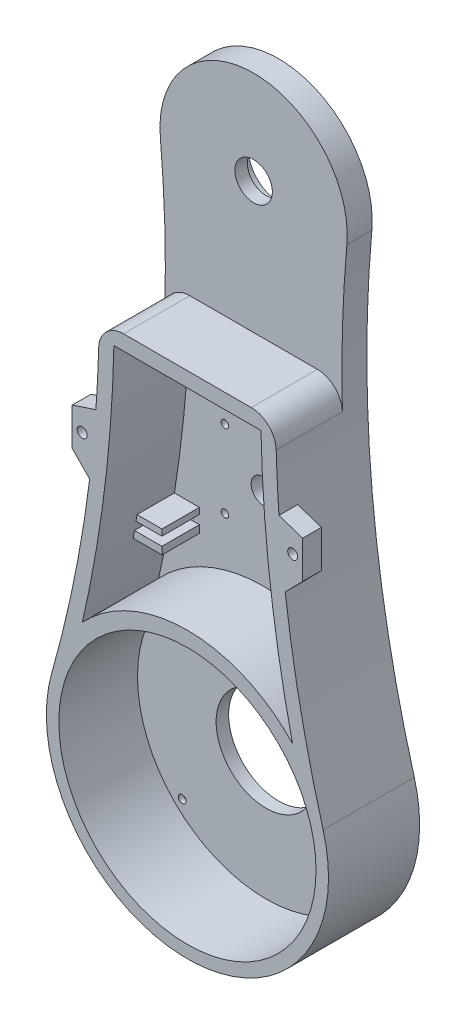
SolidWorks part; units mm, degrees
material "Custom Plastic"
ref_plane "Front Plane" through (0, 0, 0) normal (0, 0, 1) x (1, 0, 0)
ref_plane "Top Plane" through (0, 0, 0) normal (0, 1, 0) x (1, 0, 0)
ref_plane "Right Plane" through (0, 0, 0) normal (1, 0, 0) x (0, 0, -1)
sketch "Sketch1" plane through (0, 0, 0) normal (0, 0, 1) x (1, 0, 0)
  line L0 (0, 25) -> (0, 200) construction
  line L1 (-535.3493, 151.965) -> (0, 0) construction
  line L2 (-535.3493, 151.965) -> (0, 200) construction
  line L3 (0, 200) -> (0, 237.5) construction
  line L4 (0, -25) -> (0, -56.5) construction
  arc A0 (-54.3526, 15.4286) -> (54.3526, 15.4286) centre (0, 0) ccw
  arc A1 (37.35, 196.6487) -> (-37.35, 196.6487) centre (0, 200) ccw
  arc A2 (-54.3526, 15.4286) -> (-37.35, 196.6487) centre (-535.3493, 151.965) ccw
  circle A3 centre (0, 0) radius 20
  arc A4 (54.3526, 15.4286) -> (37.35, 196.6487) centre (535.3493, 151.965) cw
  circle A5 centre (0, 200) radius 7.5
  dimension "D1" = 113
  dimension "D3" = 75
  dimension "D4" = 500
  dimension "D5" = 40
  dimension "D6" = 15
  dimension "D2" = 200
extrude "Boss-Extrude1" add sketch "Sketch1" along normal blind 36.5
sketch "Sketch4" plane through (0, 0, 36.5) normal (0, 0, 1) x (1, 0, 0)
  circle A0 centre (0, 0) radius 51.5
  dimension "D1" = 103
extrude "Cut-Extrude3" cut sketch "Sketch4" against normal offset from surface (31.5 mm away) 5 up to face at (0, 97.8792, 0)
sketch "Sketch5" plane through (0, 0, 0) normal (1, 0, 0) x (0, 0, -1)
  line L0 (-10, 237.5) -> (-10, 147.5)
  line L1 (0, 237.5) -> (-36.5, 237.5) construction
  line L2 (-10, 147.5) -> (-36.5, 147.5)
  line L3 (-36.5, 196.6487) -> (-36.5, 15.4286) construction
  line L4 (0, 196.6487) -> (0, 237.5) construction
  line L5 (-36.5, 147.5) -> (-36.5, 237.5)
  line L6 (-36.5, 237.5) -> (-10, 237.5)
  dimension "D1" = 10
  dimension "D2" = 90
extrude "Cut-Extrude4" cut sketch "Sketch5" against normal through all both and the other way through all
shell "Shell1" thickness 6 removed face at (0, 63.1641, 36.5)
ref_plane "Plane1" through (0, 0, 36.5) normal (0, 0, 1) x (1, 0, 0)
sketch "Sketch7" plane through (0, 0, 36.5) normal (0, 0, 1) x (1, 0, 0)
  line L0 (-39.1592, 90.3586) -> (-46.1592, 97.5)
  line L1 (-46.1592, 97.5) -> (-46.1592, 112.5)
  line L2 (-46.1592, 112.5) -> (-36.6696, 115.6539)
  line L3 (-35.3693, 147.5) -> (35.3693, 147.5) construction
  line L4 (0, 147.5) -> (0, 57.5) construction
  line L5 (-35.3693, 147.5) -> (35.3693, 147.5) construction
  line L6 (46.1592, 97.5) -> (46.1592, 112.5)
  line L7 (39.1592, 90.3586) -> (46.1592, 97.5)
  line L8 (46.1592, 112.5) -> (36.6696, 115.6539)
  arc A0 (35.3693, 147.5) -> (54.3526, 15.4286) centre (535.3493, 151.965) ccw construction
  arc A1 (-54.3526, 15.4286) -> (-35.3693, 147.5) centre (-535.3493, 151.965) ccw construction
  arc A2 (35.3693, 147.5) -> (54.3526, 15.4286) centre (535.3493, 151.965) ccw
  arc A3 (-39.1592, 90.3586) -> (-36.6696, 115.6539) centre (-535.3493, 151.965) ccw
  circle A4 centre (-42.1592, 105) radius 2
  arc A5 (42.077, 39.189) -> (-42.077, 39.189) centre (0, 0) ccw construction
  circle A6 centre (42.1592, 105) radius 2
  arc A7 (39.1592, 90.3586) -> (36.6696, 115.6539) centre (535.3493, 151.965) cw
  point P8 (-46.1592, 105)
  dimension "D1" = 4
  dimension "D2" = 15
  dimension "D3" = 7
  dimension "D4" = 10
  dimension "D5" = 4
  dimension "D6" = 35
extrude "Boss-Extrude2" add sketch "Sketch7" against normal blind 7.5 contours A3 L2 L1 L0 | L6 L8 A7 L7 | A4 | A6
ref_plane "Plane2" through (0, 0, 6) normal (0, 0, 1) x (1, 0, 0)
sketch "Sketch8" plane through (0, 0, 6) normal (0, 0, 1) x (1, 0, 0)
  line L0 (-35.7078, 72) -> (-25.7078, 72)
  line L1 (-25.7078, 72) -> (-25.7078, 69.5)
  line L2 (-25.7078, 69.5) -> (-36.1144, 69.5)
  line L3 (-36.7051, 66) -> (-25.7078, 66)
  line L4 (-25.7078, 66) -> (-25.7078, 63)
  line L5 (-25.7078, 63) -> (-37.2316, 63)
  line L6 (-25.7078, 72) -> (-25.7078, 63) construction
  line L7 (0, 57.5) -> (0, 147.5) construction
  line L8 (-35.3693, 147.5) -> (35.3693, 147.5) construction
  line L9 (25.7078, 72) -> (25.7078, 63) construction
  line L10 (25.7078, 63) -> (37.2316, 63)
  line L11 (25.7078, 66) -> (25.7078, 63)
  line L12 (36.7051, 66) -> (25.7078, 66)
  line L13 (25.7078, 69.5) -> (36.1144, 69.5)
  line L14 (25.7078, 72) -> (25.7078, 69.5)
  line L15 (35.7078, 72) -> (25.7078, 72)
  arc A1 (-42.077, 39.189) -> (-29.4575, 141.5) centre (-535.3493, 151.965) ccw construction
  arc A2 (42.077, 39.189) -> (-42.077, 39.189) centre (0, 0) ccw construction
  arc A3 (-37.2316, 63) -> (-36.7051, 66) centre (-535.3493, 151.965) ccw
  arc A4 (42.077, 39.189) -> (-42.077, 39.189) centre (0, 0) ccw construction
  arc A5 (-36.1144, 69.5) -> (-35.7078, 72) centre (-535.3493, 151.965) ccw
  arc A6 (36.1144, 69.5) -> (35.7078, 72) centre (535.3493, 151.965) cw
  arc A7 (37.2316, 63) -> (36.7051, 66) centre (535.3493, 151.965) cw
  point P13 (0, 57.5)
  dimension "D1" = 10
  dimension "D2" = 2.5
  dimension "D3" = 12
  dimension "D4" = 3.5
  dimension "D5" = 3
extrude "Boss-Extrude3" add sketch "Sketch8" along normal blind 15
sketch "Sketch9" plane through (0, 0, 6) normal (0, 0, 1) x (1, 0, 0)
  line L0 (0, 57.5) -> (0, 192.5) construction
  line L1 (-15.5, 106) -> (15.5, 106) construction
  line L2 (-15.5, 106) -> (-15.5, 75) construction
  line L3 (-15.5, 75) -> (15.5, 75) construction
  line L4 (15.5, 106) -> (15.5, 75) construction
  circle A0 centre (0, 90.5) radius 5
  circle A1 centre (-15.5, 106) radius 1.5
  circle A2 centre (15.5, 106) radius 1.5
  circle A3 centre (15.5, 75) radius 1.5
  circle A4 centre (-15.5, 75) radius 1.5
  arc A5 (42.077, 39.189) -> (-42.077, 39.189) centre (0, 0) ccw construction
  circle A6 centre (0, 200) radius 7.5 construction
  point P18 (0, 106)
  dimension "D1" = 3
  dimension "D6" = 10
  dimension "D2" = 21
  dimension "D3" = 15.5
  dimension "D4" = 15.5
  dimension "D5" = 31
extrude "Cut-Extrude5" cut sketch "Sketch9" against normal up to surface (6 mm away) and the other way through all up to face at (0, 97.8792, 0)
sketch "Sketch10" plane through (0, 0, 6) normal (0, 0, 1) x (1, 0, 0)
  line L0 (-13.327, 124) -> (-1.673, 124)
  line L1 (0, 122.327) -> (0, 122.173)
  line L2 (-1.673, 120.5) -> (-13.327, 120.5)
  line L3 (-15, 122.173) -> (-15, 122.327)
  line L4 (-29.4575, 141.5) -> (29.4575, 141.5) construction
  circle A0 centre (0, 90.5) radius 5 construction
  arc A1 (-13.327, 120.5) -> (-15, 122.173) centre (-13.327, 122.173) cw
  arc A2 (0, 122.327) -> (-1.673, 124) centre (-1.673, 122.327) ccw
  arc A3 (0, 122.173) -> (-1.673, 120.5) centre (-1.673, 122.173) cw
  arc A4 (-15, 122.327) -> (-13.327, 124) centre (-13.327, 122.327) cw
  point P7 (0, 141.5)
  point P12 (-15, 120.5)
  point P15 (0, 124)
  point P18 (0, 120.5)
  point P21 (-15, 124)
  dimension "D1" = 3.5
  dimension "D2" = 15
  dimension "D3" = 30
extrude "Cut-Extrude6" cut sketch "Sketch10" against normal up to surface (6 mm away) up to face at (-14, 75, 0)
fillet "Fillet1" radius 10 2 edges at (35.3693, 147.5, 23.25) (-35.3693, 147.5, 23.25)
sketch "Sketch11" plane through (0, 0, 0) normal (0, 0, -1) x (-1, 0, 0)
  line L0 (0, 0) -> (-33.5876, 33.5876) construction
  line L1 (0, 0) -> (-46.2822, 0) construction
  circle A0 centre (0, 0) radius 47.5 construction
  circle A1 centre (-33.5876, 33.5876) radius 1.55
  circle A2 centre (33.5876, 33.5876) radius 1.55
  circle A3 centre (33.5876, -33.5876) radius 1.55
  circle A4 centre (-33.5876, -33.5876) radius 1.55
  point P5 (0, 0)
  point P6 (0, 0)
  point P16 (0, 0)
  dimension "D2" = 3.1
  dimension "D3" = 95
  dimension "D1" = 45
  dimension "D4" = 4
extrude "Cut-Extrude7" cut sketch "Sketch11" against normal through all
sketch "Sketch12" plane through (0, 0, 0) normal (0, 0, -1) x (-1, 0, 0)
  circle A0 centre (-33.5876, -33.5876) radius 1.55 construction
  circle A1 centre (33.5876, -33.5876) radius 1.55 construction
  circle A2 centre (33.5876, 33.5876) radius 1.55 construction
  circle A3 centre (-33.5876, 33.5876) radius 1.55 construction
  circle A4 centre (-33.5876, -33.5876) radius 1.55 construction
  circle A5 centre (33.5876, -33.5876) radius 1.55 construction
  circle A6 centre (33.5876, 33.5876) radius 1.55 construction
  circle A7 centre (-33.5876, 33.5876) radius 1.55 construction
  circle A8 centre (-33.5876, -33.5876) radius 3.55
  circle A9 centre (33.5876, -33.5876) radius 3.55
  circle A10 centre (33.5876, 33.5876) radius 3.55
  circle A11 centre (-33.5876, 33.5876) radius 3.55
  dimension "D1" = 2
extrude "Cut-Extrude8" cut sketch "Sketch12" against normal blind 3
sketch "Sketch13" plane through (0, 0, 0) normal (0, 0, -1) x (-1, 0, 0)
  circle A0 centre (0, 200) radius 12.1
  dimension "D1" = 24.2
extrude "Cut-Extrude9" cut sketch "Sketch13" against normal blind 5
